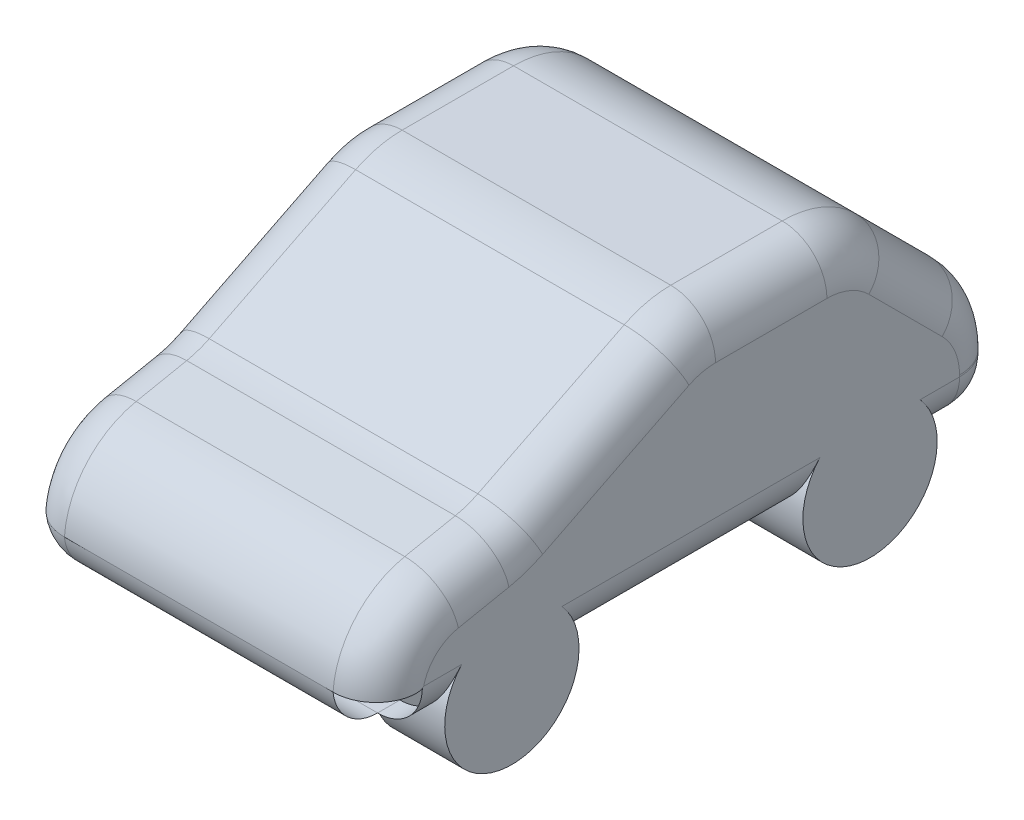
SolidWorks part; units mm, degrees
ref_plane "Ön Düzlem" through (0, 0, 0) normal (0, 0, 1) x (1, 0, 0)
ref_plane "Üst Düzlem" through (0, 0, 0) normal (0, 1, 0) x (1, 0, 0)
ref_plane "Sağ Düzlem" through (0, 0, 0) normal (1, 0, 0) x (0, 0, -1)
sketch "Çizim1" plane through (0, 0, 0) normal (1, 0, 0) x (0, 0, -1)
  line L0 (0, 5) -> (0, 3.802)
  line L1 (8.0388, 13.6078) -> (13.6868, 14.7374)
  line L2 (16.1978, 15.5989) -> (32.546, 23.773)
  line L3 (37.7436, 25) -> (50.1859, 25)
  line L4 (58.4041, 21.5959) -> (66.5959, 13.4041)
  line L5 (70, 5.1859) -> (70, 5)
  line L6 (65, 0) -> (5, 0)
  arc A0 (0, 3.802) -> (8.0388, 13.6078) centre (10, 3.802) cw
  arc A1 (13.6868, 14.7374) -> (16.1978, 15.5989) centre (11.7257, 24.5432) ccw
  arc A2 (66.5959, 13.4041) -> (70, 5.1859) centre (58.3777, 5.1859) cw
  arc A3 (50.1859, 25) -> (58.4041, 21.5959) centre (50.1859, 13.3777) cw
  arc A4 (32.546, 23.773) -> (37.7436, 25) centre (37.7436, 13.3777) cw
  arc A5 (70, 5) -> (65, 0) centre (65, 5) cw
  arc A6 (0, 5) -> (5, 0) centre (5, 5) ccw
  point P10 (0, 12)
  point P13 (15, 15)
  point P16 (70, 10)
  point P19 (55, 25)
  point P22 (35, 25)
  point P25 (70, 0)
  point P28 (0, 0)
  dimension "D9" = 10
  dimension "D10" = 10
  dimension "D11" = 11.6223
  dimension "D12" = 5
  dimension "D1" = 12
  dimension "D2" = 70
  dimension "D3" = 10
  dimension "D4" = 3
  dimension "D5" = 20
  dimension "D6" = 15
  dimension "D7" = 20
  dimension "D8" = 15
extrude "Yükseklik-Ekstrüzyon1" add sketch "Çizim1" along normal blind 40 contours A0 A6 L6 A5 L5 A2 L4 A3 L3 A4 L2 A1 L1 region at (0, 10.3988, -37.2792)
fillet "Radyus2" radius 5 22 edges at (0, 0, -35) (0, 1.4645, -68.5355) (0, 5.0929, -70) (0, 9.6335, -69.1153) (0, 17.5, -62.5) (0, 24.1153, -54.6335) (0, 25, -43.9648) (0, 24.6891, -35.0734) (0, 19.686, -24.3719) (0, 15.0844, -14.971) (0, 14.1726, -10.8628) (40, 14.1726, -10.8628) (40, 15.0844, -14.971) (40, 19.686, -24.3719) (40, 24.6891, -35.0734) (40, 25, -43.9648) (40, 24.1153, -54.6335) (40, 17.5, -62.5) (40, 9.6335, -69.1153) (40, 5.0929, -70) (40, 1.4645, -68.5355) (40, 0, -35)
sketch "Çizim2" plane through (40, 0, 0) normal (1, 0, 0) x (0, 0, -1)
  line L0 (65, 0) -> (5, 0) construction
  circle A0 centre (15, 0) radius 7.5
  circle A1 centre (55, 0) radius 7.5
  point P6 (0, 0)
  point P7 (0, 0)
  dimension "D1" = 15
  dimension "D2" = 15
  dimension "D3" = 15
extrude "Yükseklik-Ekstrüzyon2" add sketch "Çizim2" against normal blind 8
extrude "Yükseklik-Ekstrüzyon3" add sketch "Çizim2<2>" along normal blind 8 from offset 40 offset against normal yes
sketch "Çizim2<2>" plane through (40, 0, 0) normal (1, 0, 0) x (0, 0, -1) same geometry as "Çizim2"
